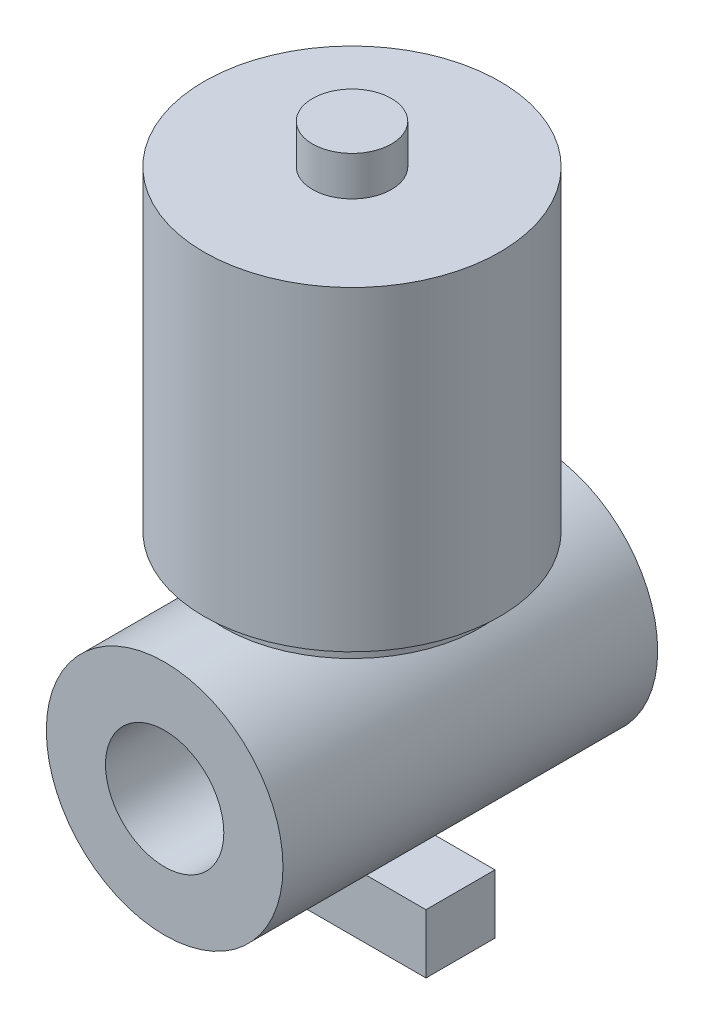
SolidWorks part; units mm, degrees
ref_plane "Front Plane" through (0, 0, 0) normal (0, 0, 1) x (1, 0, 0)
ref_plane "Top Plane" through (0, 0, 0) normal (0, 1, 0) x (1, 0, 0)
ref_plane "Right Plane" through (0, 0, 0) normal (1, 0, 0) x (0, 0, -1)
sketch "Sketch2" plane through (0, 0, 0) normal (0, 1, 0) x (1, 0, 0)
  circle A0 centre (0, 0) radius 15
  dimension "D1" = 15
extrude "Boss-Extrude1" add sketch "Sketch2" along normal blind 32
sketch "Sketch3" plane through (0, 32, 0) normal (0, 1, 0) x (1, 0, 0)
  circle A0 centre (0, 0) radius 4
  dimension "D1" = 4
extrude "Boss-Extrude2" add sketch "Sketch3" along normal blind 4
sketch "Sketch4" plane through (0, 0, 0) normal (0, -1, 0) x (-1, 0, 0)
  line L0 (15, 0) -> (-15, 0)
  circle A1 centre (0, 0) radius 15 construction
  circle A2 centre (0, 0) radius 13
  dimension "D2" = 13
  dimension "D1" = 30
extrude "Boss-Extrude3" add sketch "Sketch4" along normal blind 2 contours L0 A2 | L0 A2 region at (0, 0, 5.5174) region at (0, 0, -5.5174)
sketch "Sketch5" plane through (0, -2, 0) normal (0, -1, 0) x (-1, 0, 0)
  line L0 (-13, 0) -> (13, 0)
  circle A1 centre (0, 0) radius 13 construction
  dimension "D1" = 26
ref_plane "Plane1" through (0, 0, 0) normal (0, 0, 1) x (-1, 0, 0)
sketch "Sketch6" plane through (0, 0, 0) normal (0, 0, 1) x (-1, 0, 0)
  line L0 (0, 0) -> (0, 14)
  circle A0 centre (0, 14) radius 12
  dimension "D2" = 12
  dimension "D1" = 14
extrude "Boss-Extrude4" add sketch "Sketch6" along normal blind 19 and the other way blind 19 separate body contours A0 region at (-8.2453, -5.7547, 0)
sketch "Sketch10" plane through (0, 0, 0) normal (0, 0, 1) x (-1, 0, 0)
  line L0 (0, 0) -> (0, 29)
  line L1 (13, 0) -> (-13, 0) construction
  line L2 (-12, 14) -> (12, 14)
  line L3 (10, 26) -> (-10, 26)
  line L4 (10, 26) -> (10, 32)
  line L5 (10, 32) -> (-10, 32)
  line L6 (-10, 26) -> (-10, 32)
  line L7 (10, 26) -> (-10, 32) construction
  line L8 (10, 32) -> (-10, 26) construction
  circle A1 centre (0, 14) radius 12 construction
  circle A2 centre (0, 14) radius 6
  dimension "D2" = 24
  dimension "D3" = 6
  dimension "D1" = 29
extrude "Cut-Extrude1" cut sketch "Sketch10" against normal through all contours L0 A2 L2 | L2 A2 L0 | L0 A2 L2 | L2 A2 L0 region at (2.5465, -11.4535, 0) region at (-2.5465, -11.4535, 0) region at (2.5465, -16.5465, 0) region at (-2.5465, -16.5465, 0)
sketch "Sketch12" plane through (0, 0, 19) normal (0, 0, 1) x (1, 0, 0)
  line L0 (12, -14) -> (-12, -14)
  circle A1 centre (0, -14) radius 12 construction
  circle A2 centre (0, -14) radius 6
  dimension "D2" = 6
  dimension "D1" = 24
extrude "Cut-Extrude2" cut sketch "Sketch12" against normal through all contours L0 A2 | L0 A2 region at (0, -16.5465, 19) region at (0, -11.4535, 19)
sketch "Sketch13" plane through (0, 0, 0) normal (0, 0, 1) x (-1, 0, 0)
  line L0 (0, 0) -> (0, 29)
  line L1 (13, 0) -> (-13, 0) construction
  line L3 (11, 32) -> (-11, 32)
  line L4 (11, 32) -> (11, 26)
  line L5 (11, 26) -> (-11, 26)
  line L6 (-11, 32) -> (-11, 26)
  line L7 (11, 32) -> (-11, 26) construction
  line L8 (11, 26) -> (-11, 32) construction
  dimension "D1" = 29
extrude "Boss-Extrude5" add sketch "Sketch13" along normal blind 3.5 and the other way blind 3.5 separate body contours L3 L6 L5 L4 region at (-10.772, -29, 0)
sketch "Sketch14" plane through (0, -32, 0) normal (0, -1, 0) x (-1, 0, 0)
  line L0 (-11, 0) -> (11, 0)
  line L3 (-11, 3.5) -> (-11, -3.5) construction
  line L4 (11, 3.5) -> (11, -3.5) construction
  line L5 (-11, 0) -> (-6, 0)
  circle A0 centre (-6, 0) radius 2
  dimension "D3" = 2
  dimension "D1" = 22
  dimension "D2" = 5
extrude "Cut-Extrude3" cut sketch "Sketch14" against normal blind 3 contours A0
sketch "Sketch16" plane through (0, -32, 0) normal (0, -1, 0) x (-1, 0, 0)
  line L0 (11, 0) -> (6, 0)
  line L1 (11, 3.5) -> (11, -3.5) construction
  circle A0 centre (6, 0) radius 2
  dimension "D2" = 2
  dimension "D1" = 5
extrude "Cut-Extrude4" cut sketch "Sketch16" against normal blind 3 contours A0 region at (-4.0566, -32, 0)
